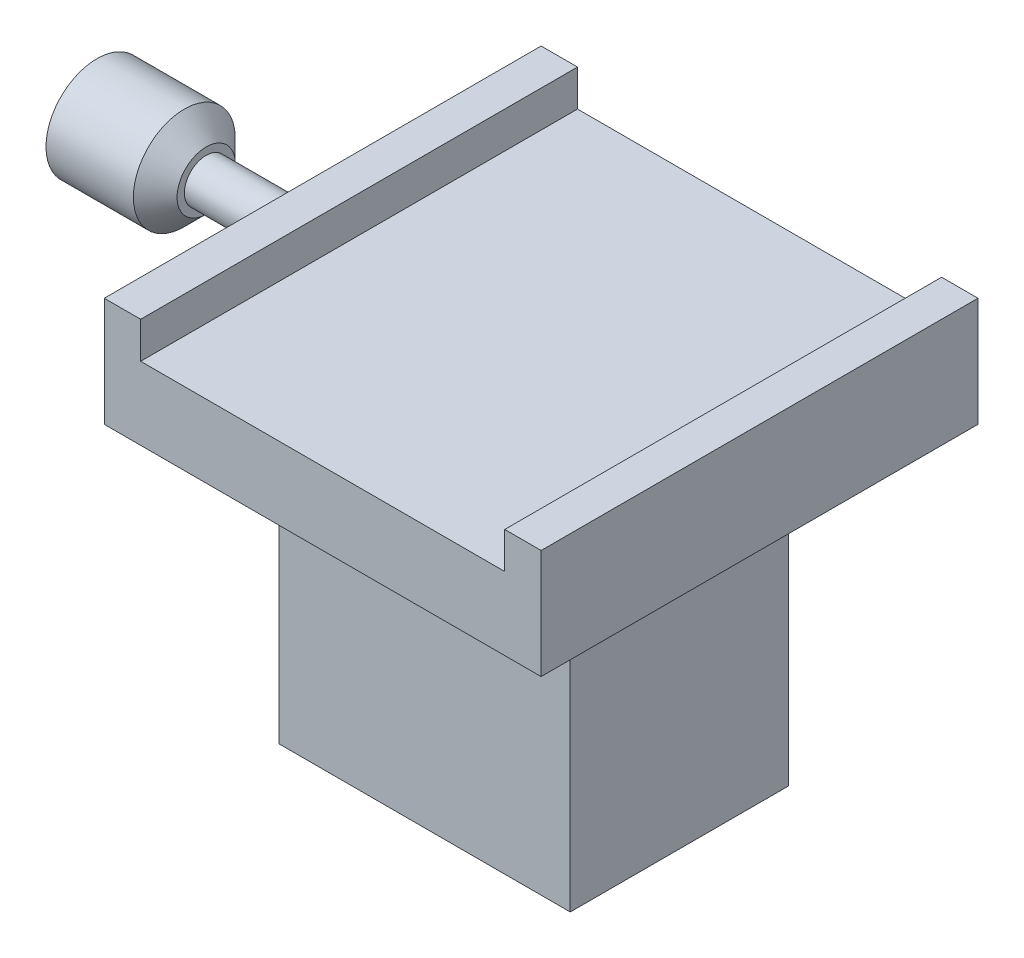
SolidWorks part; units mm, degrees
ref_plane "Front Plane" through (0, 0, 0) normal (0, 0, 1) x (1, 0, 0)
ref_plane "Top Plane" through (0, 0, 0) normal (0, 1, 0) x (1, 0, 0)
ref_plane "Right Plane" through (0, 0, 0) normal (1, 0, 0) x (0, 0, -1)
sketch "Sketch1" plane through (0, 0, 0) normal (0, 1, 0) x (1, 0, 0)
  line L1 (20, -15) -> (-20, -15)
  line L2 (20, -15) -> (20, 15)
  line L3 (20, 15) -> (-20, 15)
  line L4 (-20, -15) -> (-20, 15)
  line L5 (20, -15) -> (-20, 15) construction
  line L6 (20, 15) -> (-20, -15) construction
  point P0 (0, 0)
  dimension "D1" = 30
  dimension "D2" = 40
extrude "Boss-Extrude1" add sketch "Sketch1" against normal blind 40
ref_plane "Plane1" through (0, 0, 0) normal (0, 0, 1) x (1, 0, 0)
sketch "Sketch3" plane through (0, 0, 0) normal (0, 0, 1) x (1, 0, 0)
  line L0 (25, 15) -> (30, 15)
  line L1 (-30, 0) -> (30, 0)
  line L2 (-30, 0) -> (-30, 15)
  line L3 (-30, 15) -> (-25, 15)
  line L4 (30, 0) -> (30, 15)
  line L6 (-25, 15) -> (-25, 10)
  line L7 (-25, 10) -> (25, 10)
  line L8 (25, 15) -> (25, 10)
  dimension "D1" = 15
  dimension "D2" = 60
  dimension "D3" = 30
  dimension "D4" = 5
  dimension "D5" = 5
  dimension "D6" = 5
extrude "Boss-Extrude2" add sketch "Sketch3" along normal blind 29
extrude "Boss-Extrude3" add sketch "Sketch3<2>" against normal blind 31
sketch "Sketch3<2>" plane through (0, 0, 0) normal (0, 0, 1) x (1, 0, 0) same geometry as "Sketch3"
sketch "Sketch4" plane through (30, 0, 0) normal (1, 0, 0) x (0, 0, -1)
  line L0 (0, 30.25) -> (0, -30.25) construction
  line L1 (-29, 15) -> (31, 15) construction
  circle A0 centre (0, 7) radius 3
  dimension "D1" = 8
  dimension "D2" = 6
extrude "Boss-Extrude4" add sketch "Sketch4" against normal blind 35 from offset 55 offset against normal yes
sketch "Sketch5" plane through (-60, 0, 0) normal (-1, 0, 0) x (0, 0, 1)
  circle A0 centre (0, 7) radius 7
extrude "Boss-Extrude5" add sketch "Sketch5" against normal blind 15
chamfer "Chamfer1" distance 3 angle 45 1 edges at (-45, 7, 7)
